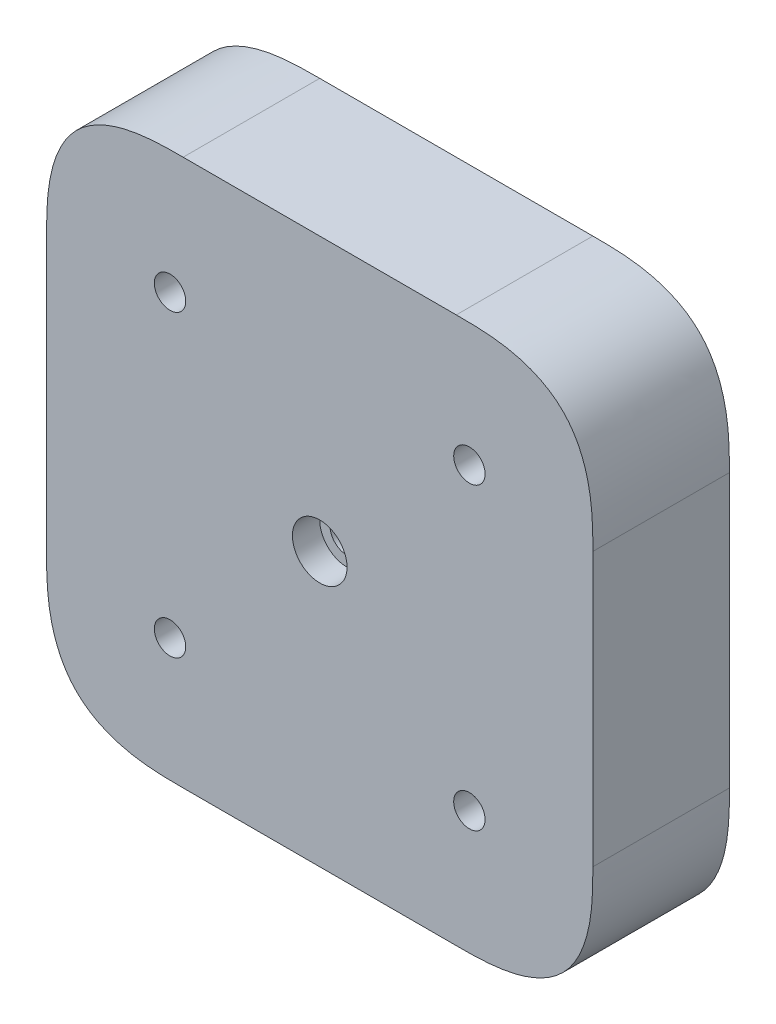
SolidWorks part; units mm, degrees
ref_plane "Plan de face" through (0, 0, 0) normal (0, 0, 1) x (1, 0, 0)
ref_plane "Plan de dessus" through (0, 0, 0) normal (0, 1, 0) x (1, 0, 0)
ref_plane "Plan de droite" through (0, 0, 0) normal (1, 0, 0) x (0, 0, -1)
sketch "Esquisse1" plane through (0, 0, 0) normal (0, 0, 1) x (1, 0, 0)
  line L0 (0, 0) -> (40, 40) construction
  line L1 (0, 0) -> (40, 0)
  line L2 (0, 0) -> (0, 40)
  line L3 (0, 40) -> (40, 40)
  line L4 (40, 0) -> (40, 40)
  line L5 (20, 20) -> (20, 40) construction
  line L7 (0, 0) -> (-7.5, 0) construction
  line L8 (0, 7.5) -> (0, 40) construction
  circle A0 centre (20, 20) radius 2
  circle A12 centre (20, 20) radius 1.25
  point P11 (-0.8, 7.4572)
  point P12 (-1.6, 47.9733)
  point P13 (1.6, 47.9733)
  point P14 (0.8, 7.4572)
  point P16 (-48, 0)
  point P24 (0, 7.5)
  point P50 (-0.269, -0.0396)
  point P64 (0, 0)
  point P71 (0, 0)
  dimension "D3" = 4
  dimension "D4" = 2.5
  dimension "D1" = 40
  dimension "D2" = 40
extrude "Boss.-Extru.1" add sketch "Esquisse1" along normal blind 10 contours L1 L4 L3 L2 A0 region at (0.5657, 20, 0)
extrude "Boss.-Extru.2" add sketch "Esquisse1<3>" along normal blind 8 contours A0 A12 region at (18.0566, 20, 0)
sketch "Esquisse1<3>" plane through (0, 0, 0) normal (0, 0, 1) x (1, 0, 0) same geometry as "Esquisse1"
sketch "Esquisse2" plane through (0, 0, 0) normal (0, 0, -1) x (-1, 0, 0)
  line L1 (-40, 0) -> (0, 40) construction
  circle A11 centre (-9.0398, 30.9602) radius 1.15
  circle A12 centre (-9.0398, 9.0398) radius 1.15
  circle A13 centre (-30.9602, 9.0398) radius 1.15
  circle A14 centre (-30.9602, 30.9602) radius 1.15
  circle A15 centre (-9.0398, 30.9602) radius 3
  circle A16 centre (-9.0398, 9.0398) radius 3
  circle A17 centre (-30.9602, 9.0398) radius 3
  circle A18 centre (-30.9602, 30.9602) radius 3
  point P5 (-20, 20)
  point P15 (-20, 20)
  point P24 (-20, 20)
  dimension "D1" = 2.3
  dimension "D2" = 15.5
  dimension "D4" = 6
  dimension "D5" = 4
  dimension "D3" = 4
extrude "Enlèv. mat.-Extru.1" cut sketch "Esquisse2" against normal up to next contours A11 | A14 | A13 | A12
extrude "Enlèv. mat.-Extru.2" cut sketch "Esquisse2<5>" against normal blind 4
sketch "Esquisse2<5>" plane through (0, 0, 0) normal (0, 0, -1) x (-1, 0, 0) same geometry as "Esquisse2"
fillet "Congé1" radius 10 4 edges at (0, 0, 5) (0, 40, 5) (40, 40, 5) (40, 0, 5) curvature continuous yes
